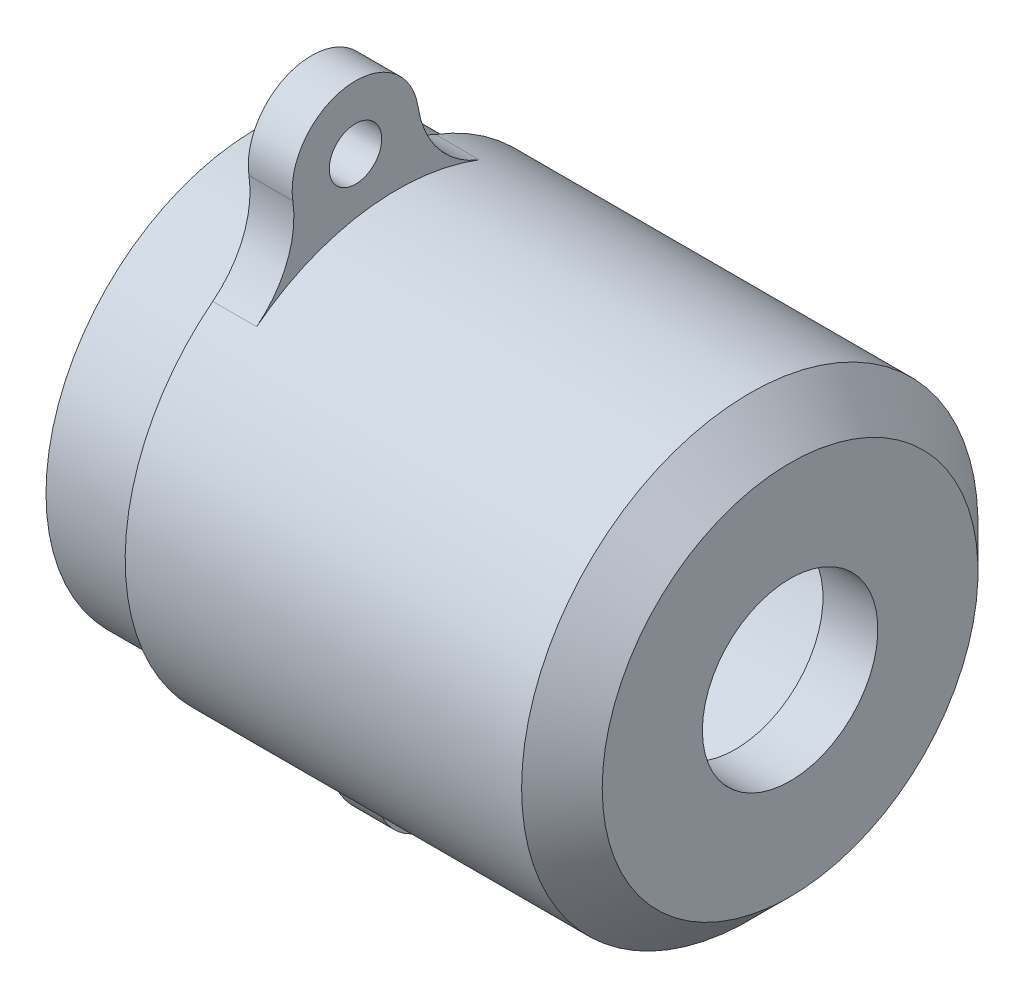
SolidWorks part; units mm, degrees
material "6061-T6 (SS)"
ref_plane "Front Plane" through (0, 0, 0) normal (0, 0, 1) x (1, 0, 0)
ref_plane "Top Plane" through (0, 0, 0) normal (0, 1, 0) x (1, 0, 0)
ref_plane "Right Plane" through (0, 0, 0) normal (1, 0, 0) x (0, 0, -1)
other "Center of Mass"
sketch "Sketch1" plane through (-31.75, 0, 0) normal (1, 0, 0) x (0, 0, -1)
  line L0 (0, 0) -> (-3.0235, 20.259) construction
  line L1 (-0.1715, 16.6719) -> (1.509, 20.9354) construction
  line L2 (1.509, 20.9354) -> (-1.3431, 24.5225) construction
  line L3 (-1.3431, 24.5225) -> (-5.8756, 23.846) construction
  line L4 (-5.8756, 23.846) -> (-7.5561, 19.5825) construction
  line L5 (-7.5561, 19.5825) -> (-4.704, 15.9955) construction
  line L6 (-4.704, 15.9955) -> (-0.1715, 16.6719) construction
  line L7 (4.704, -15.9955) -> (0.1715, -16.6719) construction
  line L8 (0.1715, -16.6719) -> (-1.509, -20.9354) construction
  line L9 (-1.509, -20.9354) -> (1.3431, -24.5225) construction
  line L10 (1.3431, -24.5225) -> (5.8756, -23.846) construction
  line L11 (5.8756, -23.846) -> (7.5561, -19.5825) construction
  line L12 (7.5561, -19.5825) -> (4.704, -15.9955) construction
  line L13 (-7.5561, 19.5825) -> (1.509, 20.9354) construction
  line L15 (0, 0) -> (12.0871, 1.8039) construction
  circle A0 centre (0, 0) radius 13.9746
  circle A1 centre (0, 0) radius 16.5146 construction
  circle A3 centre (3.0235, -20.259) radius 3.9688 construction
  circle A4 centre (-3.0235, 20.259) radius 8.6143 construction
  arc A8 (-10.1777, 13.0056) -> (-5.9368, -15.4106) centre (0, 0) ccw
  arc A9 (5.9368, 15.4106) -> (10.1777, -13.0056) centre (0, 0) cw
  circle A16 centre (-3.0235, 20.259) radius 2.667 construction
  circle A17 centre (3.0235, -20.259) radius 2.667 construction
  arc A18 (-9.6563, 36.4316) -> (-11.3683, 23.9475) centre (128.3504, 11.1461) ccw construction
  arc A19 (4.4855, 36.4316) -> (4.6428, 28.4562) centre (76.9323, 33.8717) ccw construction
  arc A20 (-10.1777, 13.0056) -> (-7.5561, 19.5825) centre (-14.5121, 18.5444) ccw
  arc A21 (-7.5561, 19.5825) -> (1.509, 20.9354) centre (-3.0235, 20.259) cw
  arc A22 (1.509, 20.9354) -> (5.9368, 15.4106) centre (8.4651, 21.9736) ccw
  arc A23 (7.5561, -19.5825) -> (10.1777, -13.0056) centre (14.5121, -18.5444) cw
  arc A24 (-1.509, -20.9354) -> (7.5561, -19.5825) centre (3.0235, -20.259) ccw
  arc A25 (-5.9368, -15.4106) -> (-1.509, -20.9354) centre (-8.4651, -21.9736) cw
  point P4 (-2.4377, 16.3337)
  dimension "D1" = 27.9492
  dimension "D4" = 5.334
  dimension "D2" = 2.54
  dimension "D3" = 7.9375
extrude "Boss-Extrude1" add sketch "Sketch1" along normal blind 3.175
sketch "Sketch2" plane through (-28.575, 0, 0) normal (1, 0, 0) x (0, 0, -1)
  circle A0 centre (0, 0) radius 13.9746
  circle A1 centre (0, 0) radius 16.5146
  arc A2 (-10.1777, 13.0056) -> (-5.9368, -15.4106) centre (0, 0) ccw construction
  circle A3 centre (0, 0) radius 13.9746 construction
extrude "Boss-Extrude2" add sketch "Sketch2" along normal up to surface (24.4625 mm away)
sketch "Sketch5" plane through (0, 0, 0) normal (0, 0, 1) x (1, 0, 0)
  line L1 (-0.1437, 13.598) -> (-0.1437, 6.35)
  line L3 (-4.1125, -16.5146) -> (-4.1125, 16.5146) construction
  line L4 (-4.1125, 6.35) -> (-4.1125, 16.5146)
  line L5 (0, 0) -> (45.5597, 0) construction
  line L6 (-4.1125, 6.35) -> (-0.1437, 6.35)
  line L7 (-4.1125, 16.5146) -> (-3.0604, 16.5146)
  line L8 (-3.0604, 16.5146) -> (-0.1437, 13.598)
  line L9 (-4.1125, 13.9746) -> (-2.3164, 15.7707) construction
  dimension "D2" = 3.9688
  dimension "D1" = 12.7
  dimension "D3" = 45
  dimension "D4" = 2.54
  dimension "D5" = 2.54
revolve "Revolve1" add sketch "Sketch5" angle 360 about L5
sketch "Sketch3" plane through (-31.75, 0, 0) normal (-1, 0, 0) x (0, 0, 1)
  circle A0 centre (0, 0) radius 13.9746
  circle A1 centre (0, 0) radius 15.2446
  circle A2 centre (0, 0) radius 13.9746 construction
  dimension "D1" = 1.27
extrude "Boss-Extrude3" add sketch "Sketch3" along normal blind 7
sketch "Sketch6" plane through (0, 0, 0) normal (0, 0, 1) x (1, 0, 0)
  line L0 (-31.75, -24.8417) -> (-30.8543, -24.8417)
  line L1 (-31.75, -24.8417) -> (-28.575, -24.8417) construction
  line L2 (-31.75, -24.8417) -> (-31.75, -21.59)
  line L3 (-31.75, -19.5825) -> (-31.75, -24.8417) construction
  arc A0 (-31.75, -21.59) -> (-28.6918, -27.0202) centre (-25.4, -21.59) ccw construction
  arc A1 (-30.8543, -24.8417) -> (-31.75, -21.59) centre (-25.4, -21.59) cw
extrude "Cut-Extrude1" cut sketch "Sketch6" against normal through all both and the other way through all
hole_wizard "#6 Clearance Hole1" positions "Sketch7" profile "Sketch8" hole size "#6" standard "ANSI Inch" end condition up to next
sketch "Sketch7" plane through (-28.575, 0, 0) normal (1, 0, 0) x (0, 0, -1)
  point P0 (-3.0235, 20.259)
  point P3 (3.0235, -20.259)
sketch "Sketch8" plane through (-28.575, 20.259, 3.0235) normal (0, 1, 0) x (0, 0, -1)
  line L0 (0, 0) -> (0, 3.175)
  line L1 (0, 3.175) -> (1.8986, 3.175)
  line L2 (1.8986, 3.175) -> (1.8986, 0)
  line L5 (1.8986, 0) -> (0, 0)
  line L11 (0, -6.35) -> (0, 107.95) construction
  dimension "Thru Hole Dia." = 3.7973
  dimension "Thru Hole Depth" = 3.175
equation "\"motor diameter\"= 28mm"
equation "\"D1@Sketch1\"=\"motor diameter\"-0.002in"
equation "\"D1@Boss-Extrude3\"=7mm"
equation "\"D2@Sketch5\"=5/32"
